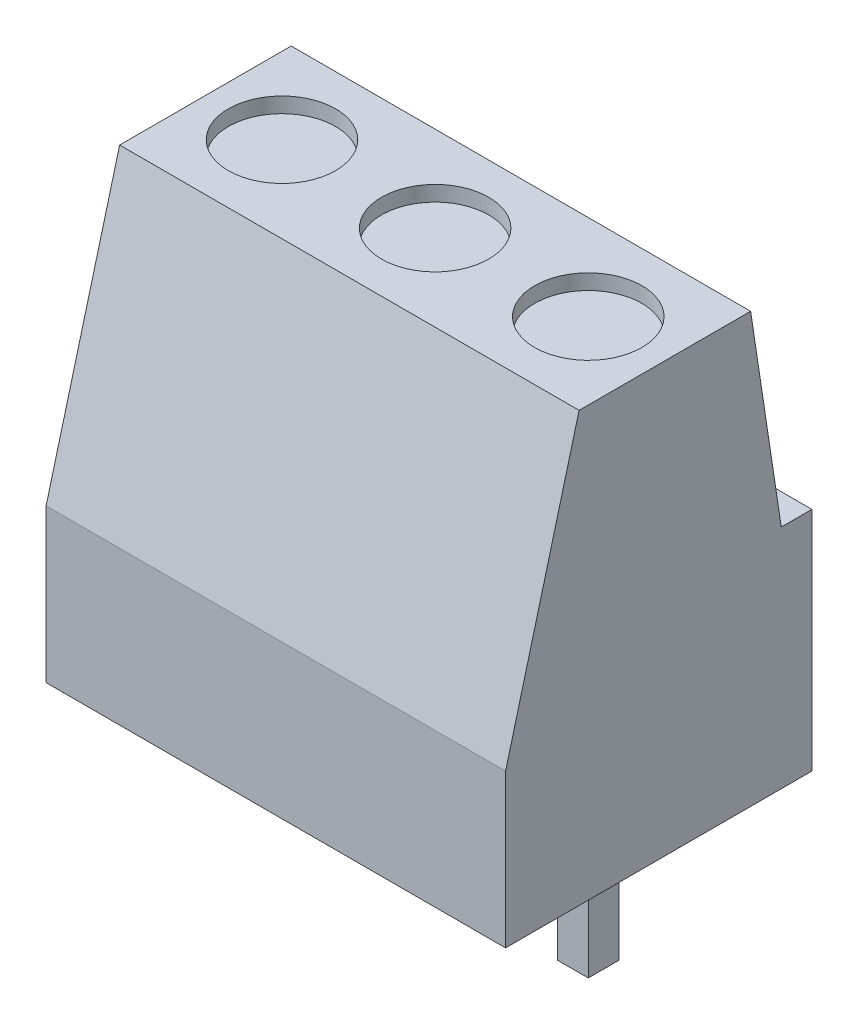
SolidWorks part; units mm, degrees
ref_plane "Front Plane" through (0, 0, 0) normal (0, 0, 1) x (1, 0, 0)
ref_plane "Top Plane" through (0, 0, 0) normal (0, 1, 0) x (1, 0, 0)
ref_plane "Right Plane" through (0, 0, 0) normal (1, 0, 0) x (0, 0, -1)
sketch "Sketch3" plane through (0, 0, 0) normal (0, 1, 0) x (1, 0, 0)
  line L0 (0, -5) -> (0, 5) construction
  line L1 (-7.5, 5) -> (7.5, 5)
  line L2 (-7.5, 5) -> (-7.5, -5)
  line L3 (-7.5, -5) -> (7.5, -5)
  line L4 (7.5, 5) -> (7.5, -5)
  line L9 (7.5, 0) -> (-7.5, 0) construction
  point P8 (0, 0)
  dimension "D1" = 10
  dimension "D2" = 15
extrude "Boss-Extrude3" add sketch "Sketch3" along normal blind 14 separate body
sketch "Sketch4" plane through (-7.5, 0, 0) normal (-1, 0, 0) x (0, 0, 1)
  line L2 (-4, 7.4) -> (-3, 14)
  line L3 (-3, 14) -> (-5, 14)
  line L6 (5, 14) -> (2.6, 14)
  line L7 (2.6, 14) -> (5, 5)
  line L10 (-3, 14) -> (2.6, 14) construction
  line L12 (5, 14) -> (5, 0) construction
  line L13 (5, 5) -> (5, 14)
  line L14 (-5, 14) -> (5, 14) construction
  line L16 (-4, 7.4) -> (-5, 7.4)
  line L17 (-5, 14) -> (-5, 0) construction
  line L18 (-5, 7.4) -> (-5, 14)
  line L20 (-5, 0) -> (5, 0) construction
  dimension "D1" = 7.4
  dimension "D2" = 2.4
  dimension "D3" = 2
  dimension "D4" = 5
  dimension "D5" = 1
extrude "Cut-Extrude1" cut sketch "Sketch4" against normal through all
sketch "Sketch5" plane through (0, 14, 0) normal (0, 1, 0) x (1, 0, 0)
  line L0 (-7.5, 0.2) -> (7.5, 0.2) construction
  line L1 (-7.5, 3) -> (-7.5, -2.6) construction
  line L2 (7.5, -2.6) -> (7.5, 3) construction
  circle A2 centre (-5, 0.2) radius 1.75
  dimension "D3" = 3.5
  dimension "D1" = 5
extrude "Cut-Extrude2" cut sketch "Sketch5" against normal blind 0.5
sketch "Sketch6" plane through (0, 0, -5) normal (0, 0, -1) x (-1, 0, 0)
  line L0 (-7.5, 0) -> (7.5, 0) construction
  line L1 (3.5, 4.4) -> (6.5, 4.4)
  line L2 (3.5, 4.4) -> (3.5, 1.4)
  line L3 (3.5, 1.4) -> (6.5, 1.4)
  line L4 (6.5, 4.4) -> (6.5, 1.4)
  point P6 (5, 1.4)
  dimension "D1" = 3
  dimension "D2" = 3
  dimension "D3" = 1.4
  dimension "D4" = 5
extrude "Cut-Extrude4" cut sketch "Sketch6" against normal blind 0.5
pattern_linear "LPattern2" count 3 spacing 5 along (1, 0, 0) of "Cut-Extrude2", "Cut-Extrude4"
sketch "Sketch7" plane through (0, 0, 0) normal (0, -1, 0) x (1, 0, 0)
  line L0 (-7.5, 0) -> (7.5, 0) construction
  line L1 (-7.5, -5) -> (-7.5, 5) construction
  line L2 (7.5, 5) -> (7.5, -5) construction
  line L4 (-5.46, -0.5) -> (-4.46, -0.5)
  line L5 (-5.46, -0.5) -> (-5.46, 0.5)
  line L6 (-5.46, 0.5) -> (-4.46, 0.5)
  line L7 (-4.46, -0.5) -> (-4.46, 0.5)
  line L8 (-5.46, -0.5) -> (-4.46, 0.5) construction
  line L9 (-5.46, 0.5) -> (-4.46, -0.5) construction
  point P6 (-4.96, 0)
  point P11 (0, 0)
  dimension "D1" = 1
  dimension "D2" = 2.54
extrude "Boss-Extrude4" add sketch "Sketch7" along normal blind 4 separate body
pattern_linear "LPattern3" count 3 spacing 5.08 along (1, 0, 0) of "Boss-Extrude4"
ref_axis "Axis1" through (-4.96, 0, 0) along (0, -1, 0)
